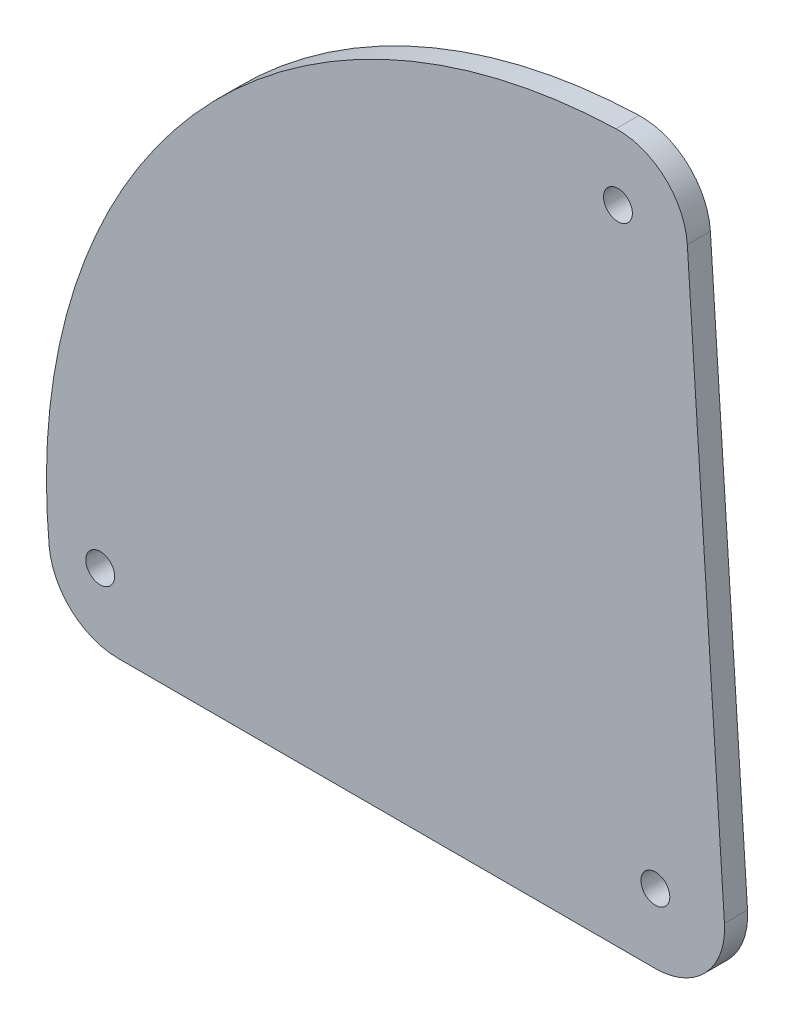
SolidWorks part; units mm, degrees
ref_plane "前视基准面" through (0, 0, 0) normal (0, 0, 1) x (1, 0, 0)
ref_plane "上视基准面" through (0, 0, 0) normal (0, 1, 0) x (1, 0, 0)
ref_plane "右视基准面" through (0, 0, 0) normal (1, 0, 0) x (0, 0, -1)
ref_plane "基准面4" through (0, 0, -18.206) normal (0, 0, 1) x (1, 0, 0)
sketch "草图1" plane through (0, 0, -18.206) normal (0, 0, 1) x (1, 0, 0)
  line L0 (3.8679, -69.618) -> (120.3, -69.618)
  line L1 (135.2682, -53.6418) -> (127.2229, 69.7096)
  circle A0 centre (120.3, -54.618) radius 3.125
  circle A1 centre (112.197, 69.618) radius 3.125
  circle A2 centre (0, -54.618) radius 3.125
  arc A3 (127.2229, 69.7096) -> (111.7717, 83.7256) centre (112.2547, 68.7334) ccw
  arc A4 (111.7717, 83.7256) -> (-11.0619, -56.0672) centre (115.8788, -43.7456) ccw
  arc A5 (-11.0619, -56.0672) -> (3.8679, -69.618) centre (3.8679, -54.618) ccw
  arc A6 (120.3, -69.618) -> (135.2682, -53.6418) centre (120.3, -54.618) ccw
  point P15 (0, 0)
  point P16 (0, 0)
  dimension "D1" = 6.25
  dimension "D2" = 6.25
  dimension "D3" = 6.25
  dimension "D4" = 120.3
  dimension "D5" = 167.4
extrude "凸台-拉伸1" add sketch "草图1" against normal blind 5
scale "缩放比例1" bodies to scale 103 scale about centroid uniform scaling yes scale factor 0.8
